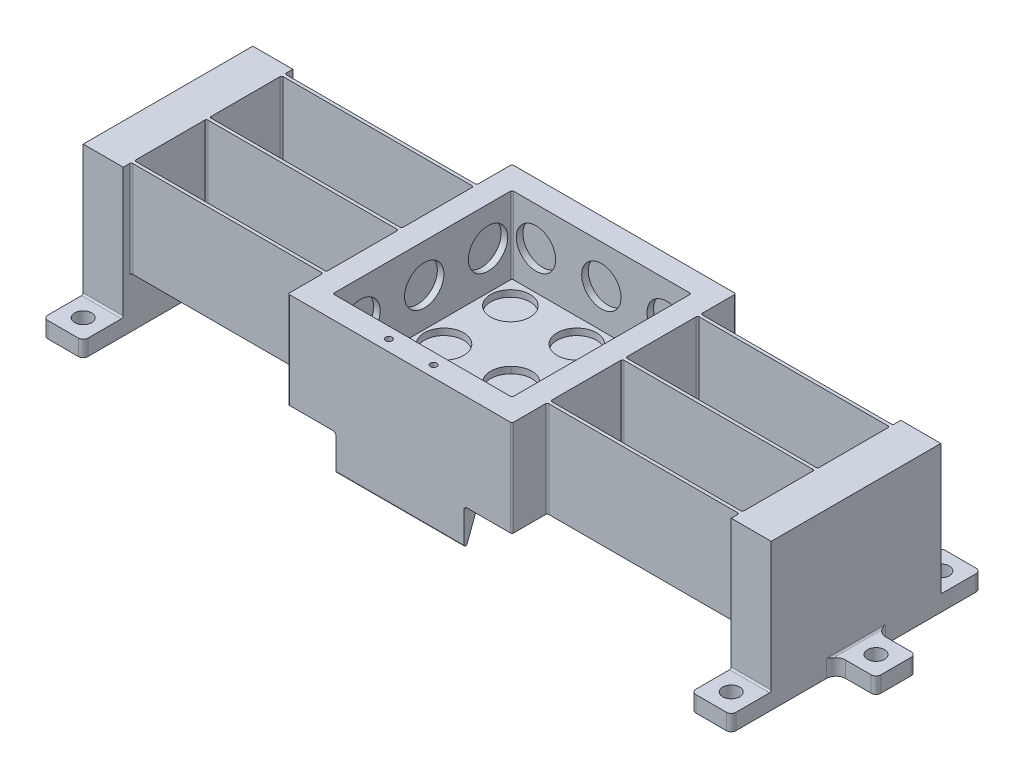
SolidWorks part; units mm, degrees
ref_plane "Front Plane" through (0, 0, 0) normal (0, 0, 1) x (1, 0, 0)
ref_plane "Top Plane" through (0, 0, 0) normal (0, 1, 0) x (1, 0, 0)
ref_plane "Right Plane" through (0, 0, 0) normal (1, 0, 0) x (0, 0, -1)
sketch "Sketch1" plane through (0, 0, 0) normal (0, 1, 0) x (1, 0, 0)
  line L1 (-35, -35) -> (35, -35)
  line L2 (-35, -35) -> (-35, 35)
  line L3 (-35, 35) -> (35, 35)
  line L4 (35, -35) -> (35, 35)
  line L5 (-35, -35) -> (35, 35) construction
  line L6 (-35, 35) -> (35, -35) construction
  point P0 (0, 0)
  dimension "D1" = 70
  dimension "D2" = 70
extrude "Boss-Extrude1" add sketch "Sketch1" along normal blind 30
shell "Shell1" thickness 7 removed face at (0, 30, 0)
sketch "Sketch2" plane through (0, 30, 0) normal (0, 1, 0) x (1, 0, 0)
  line L0 (-35, 35) -> (-35, -35) construction
  line L1 (-28, -28) -> (28, -28) construction
  line L2 (-28, -28) -> (-28, 28) construction
  line L3 (-28, 28) -> (28, 28) construction
  line L4 (28, -28) -> (28, 28) construction
  line L5 (-28, -28) -> (28, 28) construction
  line L6 (-28, 28) -> (28, -28) construction
  line L7 (35, 35) -> (-35, 35) construction
  point P0 (0, 0)
  dimension "D1" = 7
  dimension "D2" = 7
sketch "Sketch3" plane through (35, 0, 0) normal (1, 0, 0) x (0, 0, -1)
  line L0 (-35, 30) -> (35, 30) construction
  line L1 (-24, 30) -> (-23, 30)
  line L2 (-24, 30) -> (-24, 0)
  line L3 (-24, 0) -> (-23, 0)
  line L4 (-23, 30) -> (-23, 0)
  line L5 (-35, 0) -> (35, 0) construction
  line L6 (-28, 30) -> (28, 30) construction
  line L7 (-0.5, 30) -> (0.5, 30)
  line L8 (-0.5, 30) -> (-0.5, 0)
  line L9 (-0.5, 0) -> (0.5, 0)
  line L10 (0.5, 30) -> (0.5, 0)
  line L11 (28, 30) -> (-28, 30) construction
  line L12 (24, 30) -> (23, 30)
  line L13 (24, 30) -> (24, 0)
  line L14 (24, 0) -> (23, 0)
  line L15 (23, 30) -> (23, 0)
  line L16 (-23.5, 30) -> (-23.5, 0) construction
  line L17 (0, 30) -> (0, 0) construction
  line L18 (23.5, 0) -> (23.5, 30) construction
  dimension "D1" = 23
  dimension "D2" = 23
  dimension "D3" = 1
extrude "Boss-Extrude2" add sketch "Sketch3" along normal blind 60
sketch "Sketch5" plane through (95, 0, 0) normal (1, 0, 0) x (0, 0, -1)
  line L0 (-24, 30) -> (-24, 0) construction
  line L1 (-26.5, 30) -> (26.5, 30)
  line L2 (-26.5, 30) -> (-26.5, 0)
  line L3 (-26.5, 0) -> (26.5, 0)
  line L4 (26.5, 30) -> (26.5, 0)
  line L5 (28, 30) -> (-28, 30) construction
  line L6 (24, 0) -> (35, 0) construction
  line L7 (24, 0) -> (24, 30) construction
  dimension "D1" = 2.5
  dimension "D2" = 2.5
extrude "Boss-Extrude3" add sketch "Sketch5" along normal blind 12.5
sketch "Sketch6" plane through (0, 0, 0) normal (0, -1, 0) x (1, 0, 0)
  line L1 (95, 26.5) -> (107.5, 26.5)
  line L2 (95, 26.5) -> (95, -26.5)
  line L3 (95, -26.5) -> (107.5, -26.5)
  line L4 (107.5, 26.5) -> (107.5, -26.5)
extrude "Boss-Extrude4" add sketch "Sketch6" along normal blind 15.75
sketch "Sketch8" plane through (0, -15.75, 0) normal (0, -1, 0) x (1, 0, 0)
  line L1 (107.5, -26.5) -> (95, -26.5)
  line L2 (107.5, -26.5) -> (107.5, -39)
  line L3 (107.5, -39) -> (95, -39)
  line L4 (95, -26.5) -> (95, -39)
  line L5 (107.5, 26.5) -> (95, 26.5)
  line L6 (107.5, 26.5) -> (107.5, 39)
  line L7 (107.5, 39) -> (95, 39)
  line L8 (95, 26.5) -> (95, 39)
  line L13 (107.5, -26.5) -> (107.5, 26.5) construction
  line L14 (120, -6.25) -> (107.5, -6.25)
  line L15 (120, -6.25) -> (120, 6.25)
  line L16 (120, 6.25) -> (107.5, 6.25)
  line L17 (107.5, -6.25) -> (107.5, 6.25)
  line L18 (120, -6.25) -> (107.5, 6.25) construction
  line L19 (120, 6.25) -> (107.5, -6.25) construction
  line L20 (95, 0) -> (120, 0) construction
  line L21 (95, 0.5) -> (95, -0.5) construction
  point P13 (113.75, 0)
  point P19 (107.5, 0)
  point P20 (107.5, 0)
extrude "Boss-Extrude5" add sketch "Sketch8" against normal blind 5
hole_wizard "Ø5.0mm Dowel Hole1" positions "Sketch9" profile "Sketch10" hole size "Ø5.0" standard "ANSI Metric"
sketch "Sketch9" plane through (0, -10.75, 0) normal (0, 1, 0) x (1, 0, 0)
  line L0 (101.25, 39) -> (101.25, 32.75) construction
  line L1 (95, 39) -> (107.5, 39) construction
  line L2 (101.25, 32.75) -> (107.5, 32.75) construction
  line L3 (107.5, 39) -> (107.5, 26.5) construction
  line L5 (107.5, 0) -> (113.75, 0) construction
  line L6 (107.5, -6.25) -> (107.5, 6.25) construction
  line L7 (113.75, 0) -> (113.75, 6.25) construction
  line L8 (107.5, 6.25) -> (120, 6.25) construction
  line L10 (101.25, -26.5) -> (101.25, -32.75) construction
  line L11 (95, -26.5) -> (107.5, -26.5) construction
  line L12 (101.25, -32.75) -> (107.5, -32.75) construction
  line L13 (107.5, -26.5) -> (107.5, -39) construction
  point P0 (101.25, 32.75)
  point P2 (113.75, 0)
  point P4 (101.25, -32.75)
sketch "Sketch10" plane through (101.25, -10.75, -32.75) normal (1, 0, 0) x (0, 0, 1)
  line L0 (0, 0) -> (0, 18.1023)
  line L1 (0, 18.1023) -> (2.65, 16.51)
  line L2 (2.65, 16.51) -> (2.65, 0)
  line L5 (2.65, 0) -> (0, 0)
  line L10 (0, 18.1023) -> (-2.65, 16.51) construction
  line L11 (0, -6.35) -> (0, 107.95) construction
  dimension "Hole Dia." = 5.3
  dimension "Hole Depth" = 16.51
  dimension "Drill Angle" = 118
mirror "Mirror1" about plane through (0, 0, 0) normal (1, 0, 0) of "Boss-Extrude2", "Boss-Extrude3", "Boss-Extrude5", "Boss-Extrude4", "Ø5.0mm Dowel Hole1"
fillet "Fillet1" radius 0.5 30 edges at (35, 15, 23) (95, 15, 23) (35, 15, 24) (95, 15, 24) (35, 15, 0.5) (95, 15, 0.5) (35, 15, -0.5) (95, 15, -0.5) (35, 15, -23) (95, 15, -23) (35, 15, -24) (95, 15, -24) (-95, 15, 24) (-95, 15, 23) (-95, 15, 0.5) (-95, 15, -0.5) (-95, 15, -24) (-95, 15, -23) (-35, 15, 24) (-35, 15, 23) (-35, 15, 0.5) (-35, 15, -0.5) (-35, 15, -23) (-35, 15, -24) (-101.25, -10.75, -26.5) (-107.5, -10.75, 0) (-101.25, -10.75, 26.5) (101.25, -10.75, 26.5) (101.25, -10.75, -26.5) (107.5, -10.75, 0)
fillet "Fillet2" radius 1.5 12 edges at (120, -13.25, 6.25) (120, -13.25, -6.25) (107.5, -13.25, -39) (95, -13.25, -39) (107.5, -13.25, 39) (95, -13.25, 39) (-95, -13.25, -39) (-107.5, -13.25, -39) (-120, -13.25, -6.25) (-120, -13.25, 6.25) (-95, -13.25, 39) (-107.5, -13.25, 39)
sketch "Sketch11" plane through (0, 6, 0) normal (0, 1, 0) x (1, 0, 0)
  line L26 (-28, -28) -> (-28, 28) construction
  line L32 (-28, -28) -> (28, -28) construction
  circle A0 centre (-21, -21) radius 6.15
  dimension "D1" = 12.3
  dimension "D2" = 0.85
  dimension "D3" = 0.85
extrude "Cut-Extrude1" cut sketch "Sketch11" against normal blind 2.05
pattern_linear "LPattern1" count 3 spacing 20.75 along (1, 0, 0) count 3 spacing 20.75 along (0, 0, -1) of "Cut-Extrude1"
sketch "Sketch14" plane through (0, 6, 0) normal (0, 1, 0) x (1, 0, 0)
  line L0 (-28, 0) -> (0, 0) construction
  line L1 (-28, 28) -> (-28, -28) construction
  line L2 (0, 0) -> (0, -28) construction
  line L3 (-28, -28) -> (28, -28) construction
  circle A0 centre (0, 0) radius 6.15
  dimension "D1" = 12.3
extrude "Cut-Extrude4" cut sketch "Sketch14" against normal blind 2.05
sketch "Sketch12" plane through (-28, 0, 0) normal (1, 0, 0) x (0, 0, -1)
  line L5 (-28, 18) -> (-19.35, 18) construction
  line L6 (-28, 30) -> (-28, 6) construction
  circle A0 centre (-19.35, 18) radius 6.15
  dimension "D1" = 12.3
  dimension "D2" = 2.5
extrude "Cut-Extrude2" cut sketch "Sketch12" against normal blind 2.05
pattern_linear "LPattern2" count 3 spacing 19.925 along (0, 0, -1) of "Cut-Extrude2"
sketch "Sketch13" plane through (0, 0, -28) normal (0, 0, -1) x (-1, 0, 0)
  line L6 (-28, 30) -> (-28, 6) construction
  line L7 (-20.35, 18) -> (-28, 18) construction
  circle A0 centre (-20.35, 18) radius 6.15
  dimension "D1" = 12.3
  dimension "D3" = 1.5
extrude "Cut-Extrude3" cut sketch "Sketch13" along normal blind 2.05
pattern_linear "LPattern3" count 3 spacing 20.425 along (-1, 0, 0) of "Cut-Extrude3"
mirror "Mirror2" about plane through (0, 0, 0) normal (1, 0, 0) of "LPattern2", "Cut-Extrude2"
fillet "Fillet3" radius 0.5 4 edges at (28, 18, -28) (-28, 18, -28) (28, 18, 28) (-28, 18, 28)
fillet "Fillet4" radius 0.5 4 edges at (-35, 15, 35) (35, 15, 35) (-35, 15, -35) (35, 15, -35)
sketch "Sketch19" plane through (0, 0, 0) normal (1, 0, 0) x (0, 0, -1)
  line L0 (-30, 0) -> (-35, -13.25)
  line L1 (-35, -13.25) -> (-35, 0)
  line L2 (-35, 0) -> (-30, 0)
  line L3 (0, 0) -> (-30, 0) construction
  line L4 (37.5, -15.75) -> (-37.5, -15.75) construction
  dimension "D1" = 5
  dimension "D2" = 30
  dimension "D3" = 2.5
extrude "Boss-Extrude8" add sketch "Sketch19" along normal mid plane 40
sketch "Sketch20" plane through (0, 0, 0) normal (1, 0, 0) x (0, 0, -1)
  line L0 (-35, 20) -> (-42.5, 20)
  line L1 (-42.5, 20) -> (-42.5, 30)
  line L2 (-26.5, 30) -> (-42.5, 30) construction
  line L5 (-42.5, 30) -> (-40, 30)
  line L6 (-40, 30) -> (-40, 22.5)
  line L7 (-40, 22.5) -> (-35, 22.5)
  line L8 (-35, 22.5) -> (-35, 20)
  line L9 (-35, 30) -> (-35, 0) construction
  line L10 (-35, 0) -> (-35, 30) construction
  dimension "D1" = 5
  dimension "D2" = 10
  dimension "D3" = 2.5
  dimension "D4" = 2.5
extrude "Place For Sensor" [suppressed] add sketch "Sketch20" along normal mid plane 10
fillet "Place For Sensor Fillet5" [suppressed] radius 0.5
fillet "Place For Sensor Fillet6" [suppressed] radius 1.5
hole_wizard "Place For Sensor Ø3.0mm Dowel Hole2" [suppressed] positions "Sketch21" profile "Sketch22" hole size "Ø3.0" standard "ANSI Metric"
sketch "Sketch21" [suppressed] plane through (0, 0, 32.5) normal (0, 0, 1) x (1, 0, 0)
  line L0 (-2.5, 27.5) -> (2.5, 27.5) construction
  line L2 (-18, 30) -> (18, 30) construction
  line L3 (-5, 28.5) -> (-5, 20.5) construction
  line L4 (5, 28.5) -> (5, 20.5) construction
  point P0 (-2.5, 27.5)
  point P2 (2.5, 27.5)
  dimension "D1" = 2.5
  dimension "D2" = 2.5
  dimension "D3" = 2.5
sketch "Sketch22" plane through (-2.5, 27.5, 32.5) normal (1, 0, 0) x (0, -1, 0)
  line L0 (0, 0) -> (0, 2.5)
  line L1 (0, 2.5) -> (1.65, 2.5)
  line L2 (1.65, 2.5) -> (1.65, 0)
  line L5 (1.65, 0) -> (0, 0)
  line L11 (0, -6.35) -> (0, 107.95) construction
  dimension "Thru Hole Dia." = 3.3
  dimension "Thru Hole Depth" = 2.5
sketch "Sketch23" plane through (0, 30, 0) normal (0, 1, 0) x (1, 0, 0)
  line L1 (-28, -28) -> (28, -28) construction
  circle A0 centre (-7, -31.5) radius 1
  circle A1 centre (7, -31.5) radius 1
  dimension "D4" = 2
  dimension "D1" = 3.5
  dimension "D2" = 14
  dimension "D3" = 7
extrude "Cut-Extrude5" cut sketch "Sketch23" against normal blind 6
fillet "Fillet5" radius 0.5 1 edges at (0, -13.25, 35)
fillet "Fillet6" radius 1 3 edges at (-20, 0, 32.5) (20, 0, 32.5) (0, 0, 30)
fillet "Fillet8" radius 3 4 edges at (107.5, -13, 6.25) (107.5, -13, -6.25) (-107.5, -13, -6.25) (-107.5, -13, 6.25)
